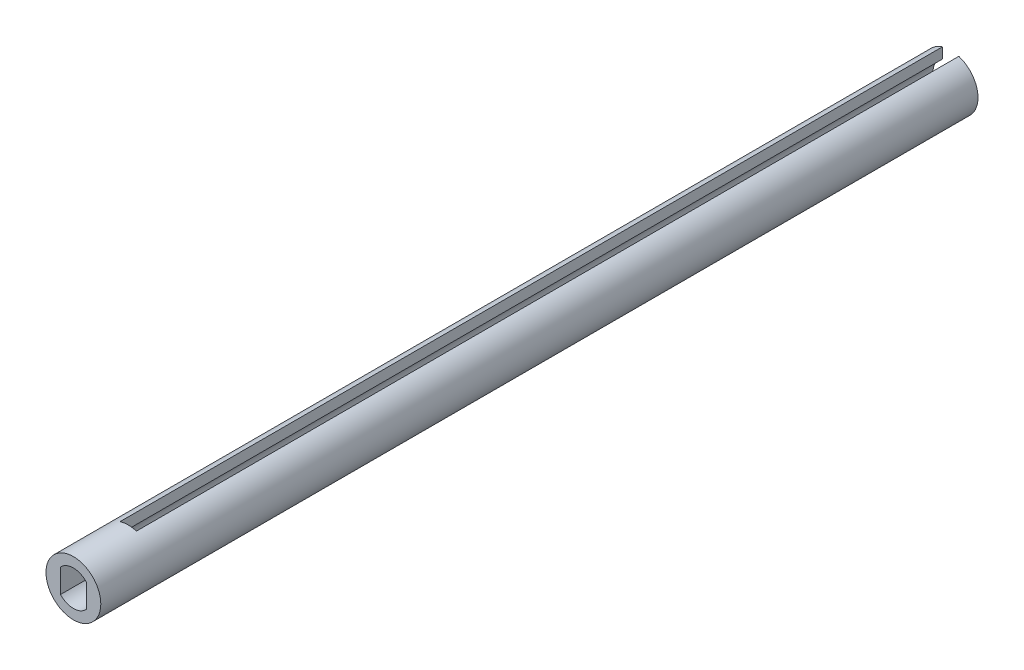
SolidWorks part; units mm, degrees
ref_plane "Front Plane" through (0, 0, 0) normal (0, 0, 1) x (1, 0, 0)
ref_plane "Top Plane" through (0, 0, 0) normal (0, 1, 0) x (1, 0, 0)
ref_plane "Right Plane" through (0, 0, 0) normal (1, 0, 0) x (0, 0, -1)
sketch "Sketch1" plane through (0, 0, 0) normal (0, 0, 1) x (1, 0, 0)
  line L0 (0, 0) -> (13912.4983, 0) construction
  line L1 (0, 0) -> (0, 13912.4983) construction
  line L2 (-2.35, 2.172) -> (-2.35, -2.172)
  line L3 (2.35, 2.172) -> (2.35, -2.172)
  circle A0 centre (0, 0) radius 3.2
  circle A1 centre (0, 0) radius 5
  dimension "D1" = 6.4
  dimension "D4" = 10
  dimension "D2" = 2.35
  dimension "D3" = 2.35
extrude "Boss-Extrude1" add sketch "Sketch1" along normal blind 160 contours L2 A0 | L3 A0 | A1 A0 region at (-2.6942, 0, 0) region at (2.6942, 0, 0) region at (-4.8586, 0, 0)
sketch "Sketch2" plane through (0, 0, 0) normal (0, 0, 1) x (1, 0, 0)
  line L0 (1.5, -5) -> (1.5, 5)
  line L1 (1.5, -5) -> (-1.5, -5)
  line L2 (1.5, 5) -> (-1.5, 5)
  line L3 (-1.5, -5) -> (-1.5, 5)
  line L4 (1.5, -5) -> (-1.5, 5) construction
  line L5 (1.5, 5) -> (-1.5, -5) construction
  line L6 (-1.5, 0) -> (1.5, 0)
  circle A0 centre (0, 0) radius 3.2
  dimension "D1" = 6.4
  dimension "D2" = 10
  dimension "D3" = 3
extrude "Cut-Extrude1" cut sketch "Sketch2" along normal blind 150 contours L0 A0 | A0 L0 L2 L3 | L3 A0 region at (2.1983, 0, 0) region at (-2.1983, 0, 0) region at (0, 4.0361, 0)
fillet "Fillet1" radius 5 2 edges at (2.35, 0, 150) (-2.35, 0, 150)
